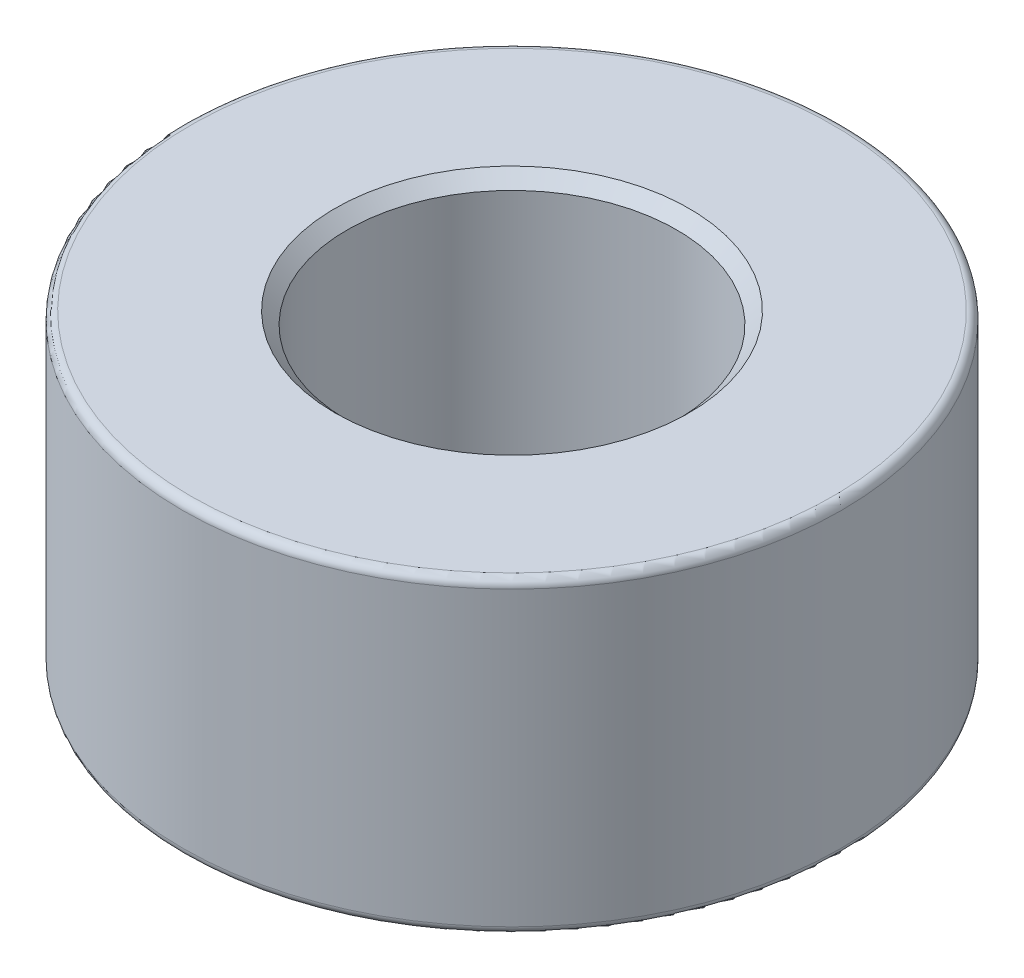
SolidWorks part; units mm, degrees
ref_plane "Front Plane" through (0, 0, 0) normal (0, 0, 1) x (1, 0, 0)
ref_plane "Top Plane" through (0, 0, 0) normal (0, 1, 0) x (1, 0, 0)
ref_plane "Right Plane" through (0, 0, 0) normal (1, 0, 0) x (0, 0, -1)
sketch "Sketch1" plane through (0, 0, 0) normal (0, 1, 0) x (1, 0, 0)
  circle A0 centre (0, 0) radius 4
  circle A1 centre (0, 0) radius 3 construction
  circle A2 centre (0, 0) radius 2
  dimension "D1" = 8
  dimension "D2" = 6
  dimension "D3" = 4
extrude "Boss-Extrude1" add sketch "Sketch1" along normal blind 1.875 and the other way blind 1.875
sketch "Sketch2" plane through (0, 0, 0) normal (0, 1, 0) x (1, 0, 0)
  line L0 (0, 3) -> (0, -3)
  circle A0 centre (0, 0) radius 3 construction
  arc A1 (0, 3) -> (0, -3) centre (0, 0) ccw
  point P5 (0, 0)
  dimension "D1" = 6
revolve "Revolve2" [suppressed] add sketch "Sketch2" angle 360 about L0
fillet "Fillet1" radius 0.1 2 edges at (0, 1.875, 4) (0, -1.875, 4)
chamfer "Chamfer4" distance 0.15 angle 45 2 edges at (0, -1.875, 2) (0, 1.875, 2)
